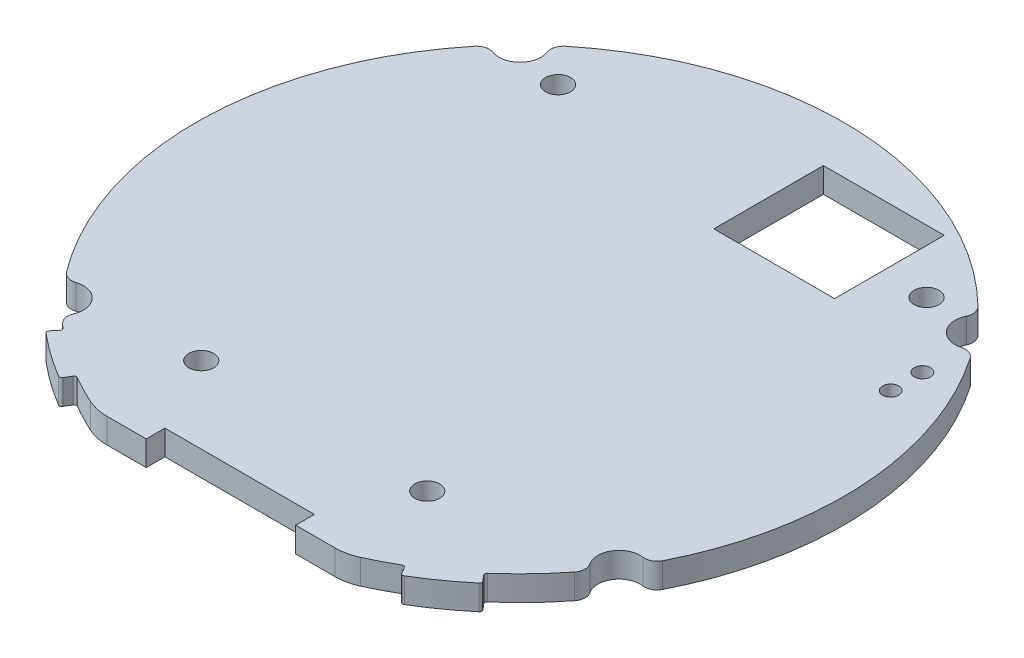
SolidWorks part; units mm, degrees
ref_plane "Front Plane" through (0, 0, 0) normal (0, 0, 1) x (1, 0, 0)
ref_plane "Top Plane" through (0, 0, 0) normal (0, 1, 0) x (1, 0, 0)
ref_plane "Right Plane" through (0, 0, 0) normal (1, 0, 0) x (0, 0, -1)
sketch "Sketch1" plane through (0, 0, 0) normal (0, 1, 0) x (1, 0, 0)
  line L0 (0, 0) -> (0, -5.9322) construction
  circle A0 centre (0, 0) radius 13
  dimension "D1" = 26
extrude "Boss-Extrude1" add sketch "Sketch1" along normal blind 1
sketch "Sketch3" plane through (0, 0, 0) normal (0, 1, 0) x (1, 0, 0)
  line L0 (-5, -12) -> (5, -12)
  line L1 (0, -12) -> (0, 0) construction
  circle A0 centre (0, 0) radius 13 construction
  arc A1 (-5, -12) -> (5, -12) centre (0, 0) ccw
  dimension "D1" = 12
extrude "Cut-Extrude2" cut sketch "Sketch3" along normal up to surface (1 mm away) up to face at (0, 1, 13)
fillet "Fillet1" radius 2 2 edges at (5, 0.5, 12) (-5, 0.5, 12)
sketch "Sketch9" plane through (0, 0, 0) normal (0, 1, 0) x (1, 0, 0)
  line L0 (1.7198, -1.2267) -> (-1.7198, 1.2267) construction
  line L1 (0, 0) -> (0, -1.5217) construction
  line L3 (0, 0) -> (-6.8087, -9.5455) construction
  circle A0 centre (0, 0) radius 11.725 construction
  point P0 (-6.8087, -9.5455)
  point P7 (0, 0)
  dimension "D3" = 23.45
  dimension "D1" = 35.5
ref_axis "Axis2" through (-6.8087, 0, 9.5455) along (0, 1, 0)
sketch "Sketch4" plane through (0, 0, 0) normal (0, -1, 0) x (1, 0, 0)
  circle A0 centre (4.4541, 8.1752) radius 0.5
  circle A1 centre (-4.6159, 8.1752) radius 0.5
  circle A2 centre (-7.0459, -8.5748) radius 0.5
  circle A3 centre (7.7441, -8.5748) radius 0.5
  dimension "D1" = 1
extrude "Cut-Extrude3" cut sketch "Sketch4" against normal up to surface (1 mm away) up to face at (0, 1, 5.727)
sketch "Sketch5" plane through (0, 1, 0) normal (0, 1, 0) x (1, 0, 0)
  line L0 (0, -0.55) -> (0, 0.55) construction
  circle A0 centre (-7, -9.8) radius 1.375
  circle A1 centre (7, -9.8) radius 1.375
  dimension "D3" = 2.75
  dimension "D1" = 7
  dimension "D2" = 9.8
sketch "Sketch6" plane through (0, 0, 0) normal (0, -1, 0) x (1, 0, 0)
  line L0 (0, 0) -> (17.8207, 0) construction
  line L1 (9.9586, -8.3562) -> (0, 0) construction
  line L2 (0, 0) -> (-9.1924, -9.1924) construction
  line L3 (10.9641, 6.9849) -> (0, 0) construction
  line L4 (-9.5846, 8.7827) -> (0, 0) construction
  circle A0 centre (9.9586, -8.3562) radius 0.85
  circle A1 centre (-9.5846, 8.7827) radius 0.85
  circle A2 centre (-9.1924, -9.1924) radius 0.85
  circle A3 centre (10.9641, 6.9849) radius 0.85
  circle A7 centre (0, 0) radius 13 construction
  dimension "D1" = 1.7
  dimension "D2" = 40
  dimension "D4" = 45
  dimension "D5" = 72.5
  dimension "D6" = 42.5
extrude "Cut-Extrude4" cut sketch "Sketch6" against normal blind 10 separate body
fillet "Fillet2" radius 0.5 8 edges at (10.4834, 0.5, -7.6876) (9.3912, 0.5, -8.9892) (-8.572, 0.5, -9.7735) (-9.7735, 0.5, -8.572) (10.4842, 0.5, 7.6865) (11.3971, 0.5, 6.2535) (-8.9902, 0.5, 9.3902) (-10.1381, 0.5, 8.1375)
sketch "Sketch10" plane through (0, 1, 0) normal (0, 1, 0) x (1, 0, 0)
  line L0 (0, 0) -> (-7.5491, -10.5835) construction
  line L1 (-6.598, -11.2012) -> (-6.8518, -11.632)
  line L2 (-8.4428, -9.8853) -> (-8.7675, -10.2655)
  line L3 (0, 0) -> (0, -18.864) construction
  line L4 (8.4428, -9.8853) -> (8.7675, -10.2655)
  line L5 (6.598, -11.2012) -> (6.8518, -11.632)
  arc A1 (-8.4428, -9.8853) -> (-6.598, -11.2012) centre (0, 0) ccw
  arc A2 (-8.7675, -10.2655) -> (-6.8518, -11.632) centre (0, 0) ccw
  arc A3 (6.8518, -11.632) -> (8.7675, -10.2655) centre (0, 0) ccw
  arc A4 (6.598, -11.2012) -> (8.4428, -9.8853) centre (0, 0) ccw
  arc A5 (-8.6753, -9.6819) -> (-5.4158, -11.8182) centre (0, 0) ccw construction
  point P19 (0, 0)
  dimension "D2" = 35.5
  dimension "D3" = 0.5
  dimension "D1" = 5
  dimension "D4" = 2
extrude "Boss-Extrude4" add sketch "Sketch10" against normal up to surface (1 mm away) up to face at (7.7441, 0, -9.0748)
fillet "Fillet4" radius 0.1 8 edges at (-8.4428, 0.5, 9.8853) (-6.598, 0.5, 11.2012) (6.598, 0.5, 11.2012) (8.4428, 0.5, 9.8853) (8.7675, 0.5, 10.2655) (6.8518, 0.5, 11.632) (-6.8518, 0.5, 11.632) (-8.7675, 0.5, 10.2655)
sketch "Sketch11" plane through (0, 0, 0) normal (0, 1, 0) x (1, 0, 0)
  line L0 (4.5826, -12) -> (-4.5826, -12) construction
  line L1 (3, -12.75) -> (-3, -12.75)
  line L2 (3, -12.75) -> (3, -11.25)
  line L3 (3, -11.25) -> (-3, -11.25)
  line L4 (-3, -12.75) -> (-3, -11.25)
  line L5 (3, -12.75) -> (-3, -11.25) construction
  line L6 (3, -11.25) -> (-3, -12.75) construction
  point P0 (0, -12)
  dimension "D1" = 1.5
  dimension "D2" = 6
extrude "Cut-Extrude6" cut sketch "Sketch11" against normal through all and the other way through all
sketch "Sketch13" plane through (0, 1, 0) normal (0, 1, 0) x (1, 0, 0)
  line L0 (5.9391, 6.6898) -> (5.9391, 11.0898)
  line L1 (5.9391, 11.0898) -> (1.0891, 11.0898)
  line L2 (1.0891, 11.0898) -> (1.0891, 6.6898)
  line L3 (1.0891, 6.6898) -> (5.9391, 6.6898)
  line L4 (10.2601, 5.8902) -> (10.2601, 4.6203) construction
  circle A0 centre (10.2601, 4.6203) radius 0.325
  circle A1 centre (10.2601, 5.8902) radius 0.325
  dimension "D1" = 0.65
  dimension "D2" = 4.4
  dimension "D3" = 4.85
  dimension "D4" = 1.0891
  dimension "D5" = 6.6898
  dimension "D6" = 1.27
  dimension "D7" = 10.2601
  dimension "D8" = 5.8902
extrude "Cut-Extrude7" cut sketch "Sketch13" against normal up to surface (1 mm away) up to face at (7.7441, 0, -9.0748)
sketch "Sketch14" plane through (0, 1, 0) normal (0, 1, 0) x (1, 0, 0)
  line L0 (0, 0) -> (0, 8.3701) construction
  line L1 (0, 0) -> (0, -8.3701) construction
  line L2 (7.395, 8.3701) -> (-7.395, 8.3701) construction
  line L3 (4.527, -8.37) -> (-4.527, -8.3701) construction
  circle A0 centre (-7.395, 8.3701) radius 0.5
  circle A1 centre (-4.527, -8.3701) radius 0.5
  circle A2 centre (4.527, -8.37) radius 0.5
  circle A3 centre (7.395, 8.3701) radius 0.5
  point P6 (0, 8.3701)
  point P10 (0, -8.3701)
  dimension "D4" = 1
  dimension "D1" = 16.7401
  dimension "D2" = 14.79
  dimension "D3" = 9.054
